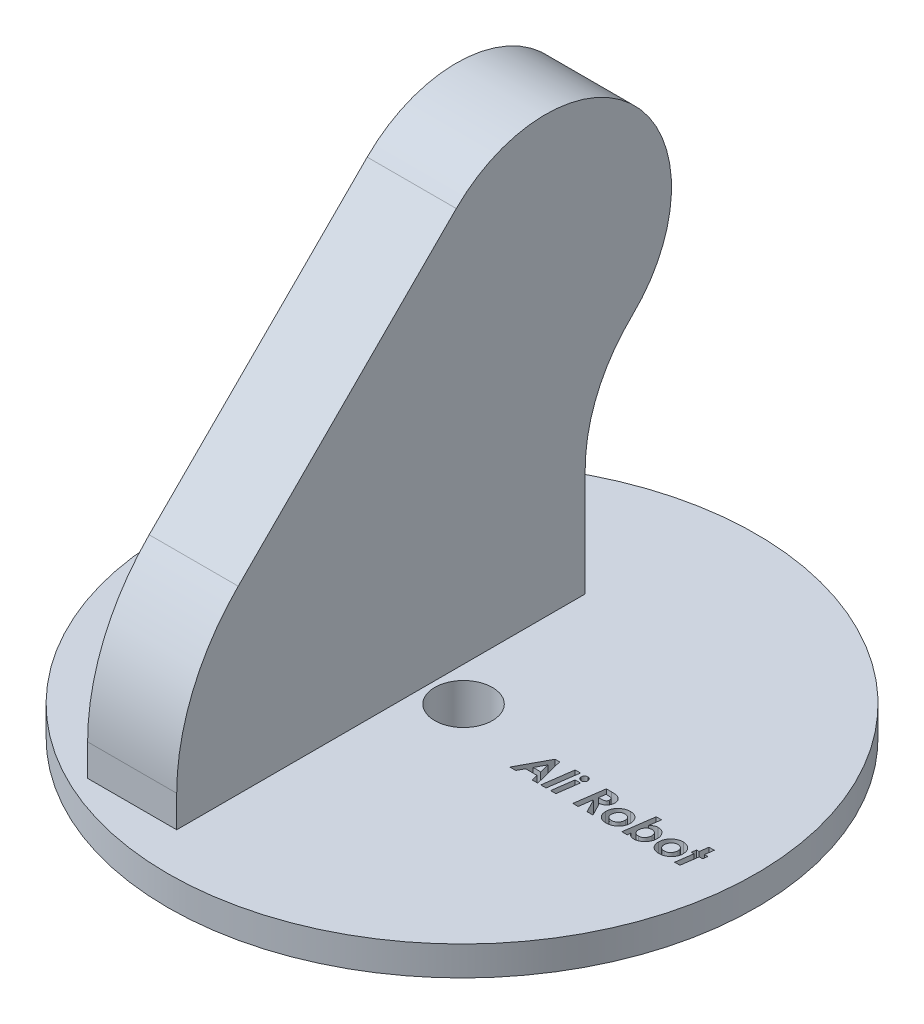
SolidWorks part; units mm, degrees
ref_plane "Front Plane" through (0, 0, 0) normal (0, 0, 1) x (1, 0, 0)
ref_plane "Top Plane" through (0, 0, 0) normal (0, 1, 0) x (1, 0, 0)
ref_plane "Right Plane" through (0, 0, 0) normal (1, 0, 0) x (0, 0, -1)
sketch "Sketch2" plane through (0, 0, 0) normal (0, 1, 0) x (1, 0, 0)
  circle A0 centre (0, 0) radius 35
  dimension "D1" = 70
extrude "Boss-Extrude1" add sketch "Sketch2" along normal blind 3.5
ref_plane "Plane1" through (-4, 0, 0) normal (1, 0, 0) x (0, 0, -1)
sketch "Sketch7" plane through (-4, 0, 0) normal (1, 0, 0) x (0, 0, -1)
  line L0 (18.6521, 16.3561) -> (18.6521, 3.5)
  line L5 (35, 3.5) -> (-35, 3.5) construction
  line L6 (-22.6311, 24.9401) -> (3.3119, 50.8831)
  line L7 (-43.5609, 3.5) -> (18.6521, 3.5)
  line L11 (-29.9535, 3.5) -> (-29.9535, 7.2624)
  arc A4 (24.252, 29.4036) -> (3.3119, 50.8831) centre (13.9185, 40.2765) ccw
  arc A5 (24.252, 29.4036) -> (18.6521, 16.3561) centre (36.6521, 16.3561) ccw
  arc A6 (-22.6311, 24.9401) -> (-29.9535, 7.2624) centre (-4.9535, 7.2624) ccw
  dimension "D1" = 25
  dimension "D4" = 30
  dimension "D3" = 18
  dimension "D5" = 45
extrude "Boss-Extrude2" add sketch "Sketch7" against normal blind 10.6 contours A5 A4 L6 L7 L0 | A4 | A4 | A4 | L6 A6 L7 region at (-4, 25.827, -1.7732)
ref_plane "Plane2" through (-6, 0, 0) normal (1, 0, 0) x (0, 0, -1)
sketch "Sketch33" plane through (0, 0, 0) normal (0, -1, 0) x (1, 0, 0)
  circle A0 centre (0, 0) radius 30
  dimension "D1" = 60
extrude "Boss-Extrude3" add sketch "Sketch33" along normal blind 2.2
sketch "Sketch35" plane through (64.9204, 3.5, -6.6124) normal (0, 1, 0) x (1, 0, 0)
  circle A0 centre (-64.8162, -6.541) radius 3.43
  dimension "D1" = 6.86
extrude "Cut-Extrude22" cut sketch "Sketch35" against normal through all
sketch "Sketch37" plane through (0, 3.5, 0) normal (0, 1, 0) x (1, 0, 0)
  line L0 (-35, 0) -> (59.3455, 0) construction
  line L1 (0, -35) -> (0, 73.7974) construction
  circle A0 centre (0, 0) radius 35 construction
sketch "Sketch38" plane through (0, 3.5, 0) normal (0, 1, 0) x (1, 0, 0)
  text T0 "<b><i>Ali Robot</i></b>"
extrude "Cut-Extrude24" cut sketch "Sketch38" against normal blind 3
